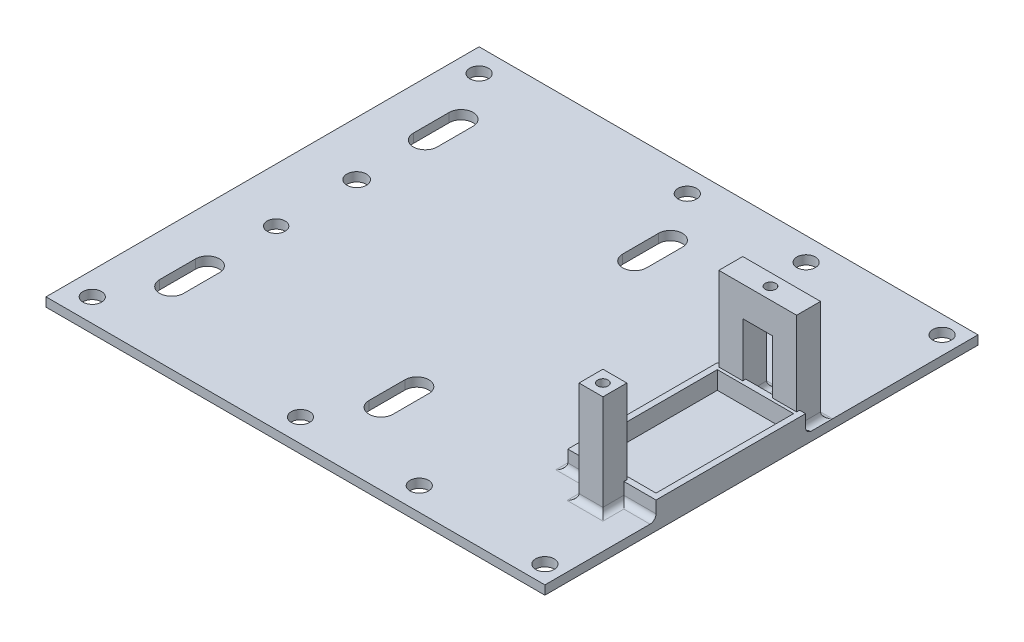
SolidWorks part; units mm, degrees
ref_plane "Přední rovina" through (0, 0, 0) normal (0, 0, 1) x (1, 0, 0)
ref_plane "Horní rovina" through (0, 0, 0) normal (0, 1, 0) x (1, 0, 0)
ref_plane "Pravá rovina" through (0, 0, 0) normal (1, 0, 0) x (0, 0, -1)
sketch "Sketch1" plane through (0, 0, 0) normal (0, 1, 0) x (1, 0, 0)
  line L0 (0, 0) -> (0, 36.2) construction
  line L1 (-31.2, 36.2) -> (31.2, 36.2)
  line L2 (-31.2, 36.2) -> (-31.2, -36.2)
  line L3 (-31.2, -36.2) -> (31.2, -36.2)
  line L4 (31.2, 36.2) -> (31.2, -36.2)
  line L5 (-31.2, 36.2) -> (31.2, -36.2) construction
  line L6 (-31.2, -36.2) -> (31.2, 36.2) construction
  line L7 (31.2, 36.2) -> (52.2, 36.2)
  line L8 (31.2, 36.2) -> (31.2, -36.2)
  line L9 (31.2, -36.2) -> (52.2, -36.2)
  line L10 (52.2, 36.2) -> (52.2, -36.2)
  line L11 (0, 0) -> (-31.2, 0) construction
  circle A0 centre (-27.333, 32.333) radius 1.55
  circle A1 centre (27.333, 32.333) radius 1.55
  circle A2 centre (27.333, -32.333) radius 1.55
  circle A3 centre (-27.333, -32.333) radius 1.55
  point P0 (0, 0)
  dimension "D4" = 3.1
  dimension "D1" = 72.4
  dimension "D2" = 62.4
  dimension "D3" = 21
  dimension "D5" = 3.867
  dimension "D6" = 3.867
extrude "Boss-Extrude1" add sketch "Sketch1" along normal blind 1.5 contours L4 L1 L2 L3 | L10 L7 L4 L9 region at (0, 0, 0) region at (41.7, 0, 0)
sketch "Sketch3" plane through (0, 1.5, 0) normal (0, 1, 0) x (1, 0, 0)
  line L0 (52.2, 36.2) -> (52.2, -36.2) construction
  line L1 (52.2, 7.375) -> (37.45, 7.375)
  line L2 (52.2, 7.375) -> (52.2, -17.625)
  line L3 (52.2, -17.625) -> (37.45, -17.625)
  line L4 (37.45, 7.375) -> (37.45, -17.625)
  line L5 (38.45, 6.375) -> (38.45, -16.625)
  line L6 (51.2, -16.625) -> (38.45, -16.625)
  line L7 (51.2, 6.375) -> (51.2, -16.625)
  line L8 (51.2, 6.375) -> (38.45, 6.375)
  circle A0 centre (44.825, 0) radius 6.375
  line M12 (52.2, -36.2) -> (52.2, 36.2)
  dimension "D1" = 25
  dimension "D2" = 14.75
  dimension "D4" = 23
  dimension "D5" = 12.75
  dimension "D3" = 1
extrude "Boss-Extrude2" add sketch "Sketch3" along normal blind 3 contours L1 L4 L3 L8 L7 L6 L5 M12 region at (51.9097, 1.5, 5.125)
sketch "Sketch4" plane through (0, 1.5, 0) normal (0, 1, 0) x (1, 0, 0)
  line L0 (37.45, -17.625) -> (52.2, -17.625) construction
  line L1 (42.825, -17.125) -> (46.825, -17.125)
  line L2 (42.825, -17.125) -> (42.825, -21.125)
  line L3 (42.825, -21.125) -> (46.825, -21.125)
  line L4 (46.825, -17.125) -> (46.825, -21.125)
  line L5 (47.2, 10.875) -> (51.2, 10.875)
  line L7 (47.2, 10.875) -> (47.2, 6.875)
  line L8 (38.2, 10.875) -> (42.2, 10.875)
  line L9 (38.2, 10.875) -> (38.2, 6.875)
  line L10 (38.2, 6.875) -> (42.2, 6.875)
  line L11 (42.2, 10.875) -> (42.2, 6.875)
  line L14 (47.2, 6.875) -> (51.2, 6.875)
  line L15 (51.2, 10.875) -> (51.2, 6.875)
  line L17 (52.2, 36.2) -> (52.2, 7.375) construction
  line L18 (51.2, 6.375) -> (38.45, 6.375) construction
  line L19 (51.2, -16.625) -> (38.45, -16.625) construction
  point P6 (44.825, -17.125)
  point P7 (44.825, -17.625)
  point P8 (42.825, -19.125)
  point P17 (47.2, 8.875)
  dimension "D1" = 4
  dimension "D2" = 4
  dimension "D3" = 2.5
  dimension "D4" = 4
  dimension "D5" = 4
  dimension "D6" = 2.5
  dimension "D7" = 5
  dimension "D8" = 4
  dimension "D9" = 1
  dimension "D10" = 4
extrude "Boss-Extrude3" add sketch "Sketch4" along normal blind 12
sketch "Sketch10" plane through (0, 13.5, 0) normal (0, 1, 0) x (1, 0, 0)
  line L0 (42.2, 10.875) -> (38.2, 10.875) construction
  line L1 (38.2, 10.875) -> (51.2, 10.875)
  line L2 (38.2, 10.875) -> (38.2, 6.875)
  line L3 (38.2, 6.875) -> (51.2, 6.875)
  line L4 (51.2, 10.875) -> (51.2, 6.875)
  line L5 (38.2, 10.875) -> (38.2, 6.875) construction
  line L6 (47.2, 6.875) -> (51.2, 6.875) construction
  line L8 (46.825, -21.125) -> (42.825, -21.125)
  line L9 (46.825, -21.125) -> (46.825, -17.125)
  line L10 (46.825, -17.125) -> (42.825, -17.125)
  line L11 (42.825, -21.125) -> (42.825, -17.125)
extrude "Boss-Extrude4" add sketch "Sketch10" along normal blind 5
sketch "Sketch5" plane through (0, 18.5, 0) normal (0, 1, 0) x (1, 0, 0)
  line L0 (46.825, -21.125) -> (42.825, -17.125) construction
  line L2 (38.2, 6.875) -> (51.2, 6.875) construction
  circle A0 centre (44.825, -19.125) radius 0.875
  circle A1 centre (44.825, 8.875) radius 0.875
  dimension "D1" = 1.75
  dimension "D2" = 1.75
  dimension "D3" = 2
extrude "Cut-Extrude1" cut sketch "Sketch5" against normal blind 4
fillet "Fillet1" radius 1 15 edges at (49.5125, 1.5, 17.625) (40.1375, 1.5, 17.625) (44.7, 1.5, -7.375) (51.7, 1.5, -7.375) (37.825, 1.5, -7.375) (38.2, 1.5, -9.125) (42.2, 1.5, -9.125) (40.2, 1.5, -10.875) (37.45, 1.5, 5.125) (42.825, 1.5, 19.375) (46.825, 1.5, 19.375) (44.825, 1.5, 21.125) (47.2, 1.5, -9.125) (51.2, 1.5, -9.125) (49.2, 1.5, -10.875)
sketch "Sketch6" plane through (0, 1.5, 0) normal (0, 1, 0) x (1, 0, 0)
  line L0 (7.473, -32.333) -> (27.333, -32.333) construction
  line L4 (7.473, 32.333) -> (27.333, 32.333) construction
  circle A4 centre (7.473, -32.333) radius 1.55
  circle A5 centre (27.333, -32.333) radius 1.55 construction
  circle A6 centre (7.473, 32.333) radius 1.55
  dimension "D2" = 19.86
  dimension "D4" = 19.86
  dimension "D1" = 3.1
  dimension "D3" = 3.1
extrude "Cut-Extrude5" cut sketch "Sketch6" against normal through all contours A4 | A6
sketch "Sketch8" plane through (0, 0, 0) normal (0, -1, 0) x (1, 0, 0)
  line L0 (-22.2, -6.73) -> (-22.2, 6.73) construction
  line L1 (-31.2, -36.2) -> (-31.2, 36.2) construction
  circle A0 centre (-22.2, -6.73) radius 1.5
  circle A1 centre (-22.2, 6.73) radius 1.5
  point P4 (-22.2, 0)
  dimension "D1" = 3
  dimension "D2" = 3
  dimension "D3" = 13.46
  dimension "D4" = 9
extrude "Cut-Extrude4" cut sketch "Sketch8" against normal through all
sketch "Sketch9" plane through (0, 1.5, 0) normal (0, 1, 0) x (1, 0, 0)
  line L0 (-22.2, 24.2) -> (-22.2, 18.2) construction
  line L1 (-20.2, 24.2) -> (-20.2, 18.2)
  line L2 (-24.2, 24.2) -> (-24.2, 18.2)
  line L3 (-22.2, -18.2) -> (-22.2, -24.2) construction
  line L4 (-20.2, -18.2) -> (-20.2, -24.2)
  line L5 (-24.2, -18.2) -> (-24.2, -24.2)
  line L6 (-22.2, 2.3889) -> (-22.2, -13.5415) construction
  line L7 (-31.2, 36.2) -> (52.2, 36.2) construction
  line L8 (-31.2, -36.2) -> (52.2, -36.2) construction
  line L9 (-4.7, 36.2) -> (-4.7, -36.2) construction
  line L10 (12.8, 24.2) -> (12.8, 18.2) construction
  line L11 (10.8, 24.2) -> (10.8, 18.2)
  line L12 (14.8, 24.2) -> (14.8, 18.2)
  line L13 (12.8, -18.2) -> (12.8, -24.2) construction
  line L14 (10.8, -18.2) -> (10.8, -24.2)
  line L15 (14.8, -18.2) -> (14.8, -24.2)
  arc A0 (-20.2, 24.2) -> (-24.2, 24.2) centre (-22.2, 24.2) ccw
  arc A1 (-24.2, 18.2) -> (-20.2, 18.2) centre (-22.2, 18.2) ccw
  arc A2 (-20.2, -18.2) -> (-24.2, -18.2) centre (-22.2, -18.2) ccw
  arc A3 (-24.2, -24.2) -> (-20.2, -24.2) centre (-22.2, -24.2) ccw
  circle A6 centre (-22.2, 6.73) radius 1.6367
  arc A7 (10.8, 24.2) -> (14.8, 24.2) centre (12.8, 24.2) cw
  arc A8 (14.8, 18.2) -> (10.8, 18.2) centre (12.8, 18.2) cw
  arc A9 (10.8, -18.2) -> (14.8, -18.2) centre (12.8, -18.2) cw
  arc A10 (14.8, -24.2) -> (10.8, -24.2) centre (12.8, -24.2) cw
  point P2 (-22.2, 21.2)
  point P7 (-22.2, -21.2)
  point P27 (12.8, 21.2)
  point P34 (12.8, -21.2)
  dimension "D1" = 2
  dimension "D2" = 2
  dimension "D3" = 6
  dimension "D4" = 6
  dimension "D5" = 15
  dimension "D6" = 15
  dimension "D7" = 17.5
extrude "Cut-Extrude6" cut sketch "Sketch9" against normal through all
sketch "Sketch11" plane through (0, 1.5, 0) normal (0, 1, 0) x (1, 0, 0)
  line L0 (46.2, -30.2) -> (52.2, -36.2) construction
  line L1 (52.2, -36.2) -> (46.2, -36.2)
  line L2 (52.2, -36.2) -> (52.2, -30.2)
  line L3 (52.2, -30.2) -> (46.2, -30.2)
  line L4 (46.2, -36.2) -> (46.2, -30.2)
  circle A0 centre (49.2, -33.2) radius 1.55
  dimension "D3" = 3.1
  dimension "D1" = 6
  dimension "D2" = 6
extrude "Cut-Extrude8" cut sketch "Sketch11" against normal up to next contours A0
mirror "Mirror1" about plane through (0, 0, 0) normal (0, 0, 1) of "Cut-Extrude8"
